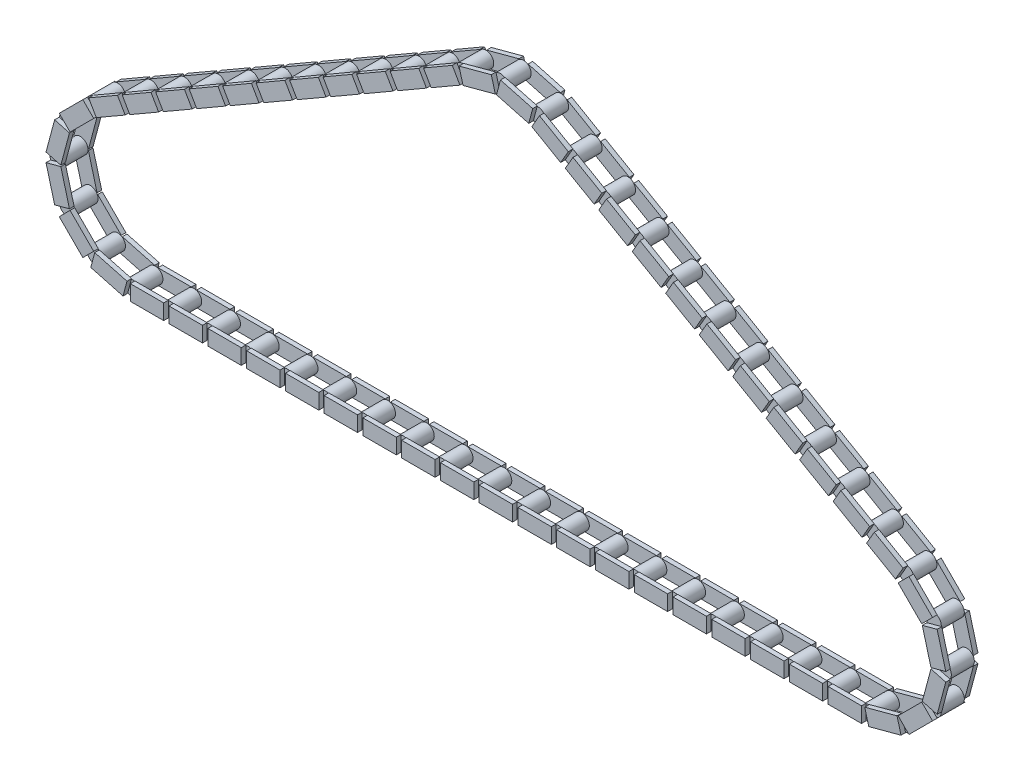
SolidWorks part; units mm, degrees
ref_plane "前视基准面" through (0, 0, 0) normal (0, 0, 1) x (1, 0, 0)
ref_plane "上视基准面" through (0, 0, 0) normal (0, 1, 0) x (1, 0, 0)
ref_plane "右视基准面" through (0, 0, 0) normal (1, 0, 0) x (0, 0, -1)
other "Configuration Table"
sketch "草图1" plane through (0, 0, 0) normal (0, 0, 1) x (1, 0, 0)
  line L0 (-97.1938, -21.2725) -> (-105.6024, -19.0195)
  line L1 (-105.6024, -19.0195) -> (-104.5671, -15.1558)
  line L2 (-104.5671, -15.1558) -> (-96.1585, -17.4088)
  line L3 (-96.1585, -17.4088) -> (-97.1938, -21.2725)
  line L4 (-107.6701, -17.8257) -> (-113.8257, -11.6701)
  line L5 (-113.8257, -11.6701) -> (-110.9972, -8.8417)
  line L6 (-110.9972, -8.8417) -> (-104.8417, -14.9972)
  line L7 (-104.8417, -14.9972) -> (-107.6701, -17.8257)
  line L8 (-115.0195, -9.6024) -> (-117.2725, -1.1938)
  line L9 (-117.2725, -1.1938) -> (-113.4088, -0.1585)
  line L10 (-113.4088, -0.1585) -> (-111.1558, -8.5671)
  line L11 (-111.1558, -8.5671) -> (-115.0195, -9.6024)
  line L12 (-117.2725, 1.1938) -> (-115.0195, 9.6024)
  line L13 (-115.0195, 9.6024) -> (-111.1558, 8.5671)
  line L14 (-111.1558, 8.5671) -> (-113.4088, 0.1585)
  line L15 (-113.4088, 0.1585) -> (-117.2725, 1.1938)
  line L16 (-113.8257, 11.6701) -> (-107.6701, 17.8257)
  line L17 (-107.6701, 17.8257) -> (-104.8417, 14.9972)
  line L18 (-104.8417, 14.9972) -> (-110.9972, 8.8417)
  line L19 (-110.9972, 8.8417) -> (-113.8257, 11.6701)
  line L20 (-106.1547, 18.9885) -> (-98.6399, 23.3272)
  line L21 (-98.6399, 23.3272) -> (-96.6399, 19.8631)
  line L22 (-96.6399, 19.8631) -> (-104.1547, 15.5244)
  line L23 (-104.1547, 15.5244) -> (-106.1547, 18.9885)
  line L24 (-97.4274, 24.0272) -> (-89.9126, 28.3659)
  line L25 (-89.9126, 28.3659) -> (-87.9126, 24.9018)
  line L26 (-87.9126, 24.9018) -> (-95.4274, 20.5631)
  line L27 (-95.4274, 20.5631) -> (-97.4274, 24.0272)
  line L28 (-88.7002, 29.0659) -> (-81.1853, 33.4046)
  line L29 (-81.1853, 33.4046) -> (-79.1853, 29.9405)
  line L30 (-79.1853, 29.9405) -> (-86.7002, 25.6018)
  line L31 (-86.7002, 25.6018) -> (-88.7002, 29.0659)
  line L32 (-79.9729, 34.1046) -> (-72.4581, 38.4433)
  line L33 (-72.4581, 38.4433) -> (-70.4581, 34.9791)
  line L34 (-70.4581, 34.9791) -> (-77.9729, 30.6405)
  line L35 (-77.9729, 30.6405) -> (-79.9729, 34.1046)
  line L36 (-71.2456, 39.1433) -> (-63.7308, 43.4819)
  line L37 (-63.7308, 43.4819) -> (-61.7308, 40.0178)
  line L38 (-61.7308, 40.0178) -> (-69.2456, 35.6791)
  line L39 (-69.2456, 35.6791) -> (-71.2456, 39.1433)
  line L40 (-62.5184, 44.1819) -> (-55.0035, 48.5206)
  line L41 (-55.0035, 48.5206) -> (-53.0035, 45.0565)
  line L42 (-53.0035, 45.0565) -> (-60.5184, 40.7178)
  line L43 (-60.5184, 40.7178) -> (-62.5184, 44.1819)
  line L44 (-53.7911, 49.2206) -> (-46.2762, 53.5593)
  line L45 (-46.2762, 53.5593) -> (-44.2762, 50.0952)
  line L46 (-44.2762, 50.0952) -> (-51.7911, 45.7565)
  line L47 (-51.7911, 45.7565) -> (-53.7911, 49.2206)
  line L48 (-45.0638, 54.2593) -> (-37.549, 58.598)
  line L49 (-37.549, 58.598) -> (-35.549, 55.1339)
  line L50 (-35.549, 55.1339) -> (-43.0638, 50.7952)
  line L51 (-43.0638, 50.7952) -> (-45.0638, 54.2593)
  line L52 (-36.3365, 59.298) -> (-28.8217, 63.6367)
  line L53 (-28.8217, 63.6367) -> (-26.8217, 60.1726)
  line L54 (-26.8217, 60.1726) -> (-34.3365, 55.8339)
  line L55 (-34.3365, 55.8339) -> (-36.3365, 59.298)
  line L56 (-27.6093, 64.3367) -> (-20.0944, 68.6754)
  line L57 (-20.0944, 68.6754) -> (-18.0944, 65.2113)
  line L58 (-18.0944, 65.2113) -> (-25.6093, 60.8726)
  line L59 (-25.6093, 60.8726) -> (-27.6093, 64.3367)
  line L60 (-18.882, 69.3754) -> (-11.3671, 73.7141)
  line L61 (-11.3671, 73.7141) -> (-9.3671, 70.25)
  line L62 (-9.3671, 70.25) -> (-16.882, 65.9113)
  line L63 (-16.882, 65.9113) -> (-18.882, 69.3754)
  line L64 (-9.6024, 74.4451) -> (-1.1938, 76.6981)
  line L65 (-1.1938, 76.6981) -> (-0.1585, 72.8344)
  line L66 (-0.1585, 72.8344) -> (-8.5671, 70.5814)
  line L67 (-8.5671, 70.5814) -> (-9.6024, 74.4451)
  line L68 (1.1938, 76.6981) -> (9.6024, 74.4451)
  line L69 (9.6024, 74.4451) -> (8.5672, 70.5814)
  line L70 (8.5672, 70.5814) -> (0.1585, 72.8344)
  line L71 (0.1585, 72.8344) -> (1.1938, 76.6981)
  line L72 (11.3672, 73.7141) -> (18.882, 69.3754)
  line L73 (18.882, 69.3754) -> (16.882, 65.9113)
  line L74 (16.882, 65.9113) -> (9.3672, 70.25)
  line L75 (9.3672, 70.25) -> (11.3672, 73.7141)
  line L76 (20.0944, 68.6754) -> (27.6093, 64.3367)
  line L77 (27.6093, 64.3367) -> (25.6093, 60.8726)
  line L78 (25.6093, 60.8726) -> (18.0944, 65.2113)
  line L79 (18.0944, 65.2113) -> (20.0944, 68.6754)
  line L80 (28.8217, 63.6367) -> (36.3365, 59.298)
  line L81 (36.3365, 59.298) -> (34.3365, 55.8339)
  line L82 (34.3365, 55.8339) -> (26.8217, 60.1726)
  line L83 (26.8217, 60.1726) -> (28.8217, 63.6367)
  line L84 (37.549, 58.598) -> (45.0638, 54.2593)
  line L85 (45.0638, 54.2593) -> (43.0638, 50.7952)
  line L86 (43.0638, 50.7952) -> (35.549, 55.1339)
  line L87 (35.549, 55.1339) -> (37.549, 58.598)
  line L88 (46.2762, 53.5593) -> (53.7911, 49.2206)
  line L89 (53.7911, 49.2206) -> (51.7911, 45.7565)
  line L90 (51.7911, 45.7565) -> (44.2762, 50.0952)
  line L91 (44.2762, 50.0952) -> (46.2762, 53.5593)
  line L92 (55.0035, 48.5206) -> (62.5184, 44.1819)
  line L93 (62.5184, 44.1819) -> (60.5184, 40.7178)
  line L94 (60.5184, 40.7178) -> (53.0035, 45.0565)
  line L95 (53.0035, 45.0565) -> (55.0035, 48.5206)
  line L96 (63.7308, 43.4819) -> (71.2456, 39.1432)
  line L97 (71.2456, 39.1432) -> (69.2456, 35.6791)
  line L98 (69.2456, 35.6791) -> (61.7308, 40.0178)
  line L99 (61.7308, 40.0178) -> (63.7308, 43.4819)
  line L100 (72.4581, 38.4433) -> (79.9729, 34.1046)
  line L101 (79.9729, 34.1046) -> (77.9729, 30.6405)
  line L102 (77.9729, 30.6405) -> (70.4581, 34.9791)
  line L103 (70.4581, 34.9791) -> (72.4581, 38.4433)
  line L104 (81.1853, 33.4046) -> (88.7002, 29.0659)
  line L105 (88.7002, 29.0659) -> (86.7002, 25.6018)
  line L106 (86.7002, 25.6018) -> (79.1853, 29.9405)
  line L107 (79.1853, 29.9405) -> (81.1853, 33.4046)
  line L108 (89.9126, 28.3659) -> (97.4274, 24.0272)
  line L109 (97.4274, 24.0272) -> (95.4274, 20.5631)
  line L110 (95.4274, 20.5631) -> (87.9126, 24.9018)
  line L111 (87.9126, 24.9018) -> (89.9126, 28.3659)
  line L112 (98.6399, 23.3272) -> (106.1547, 18.9885)
  line L113 (106.1547, 18.9885) -> (104.1547, 15.5244)
  line L114 (104.1547, 15.5244) -> (96.6399, 19.8631)
  line L115 (96.6399, 19.8631) -> (98.6399, 23.3272)
  line L116 (107.6701, 17.8257) -> (113.8257, 11.6701)
  line L117 (113.8257, 11.6701) -> (110.9972, 8.8417)
  line L118 (110.9972, 8.8417) -> (104.8417, 14.9972)
  line L119 (104.8417, 14.9972) -> (107.6701, 17.8257)
  line L120 (115.0195, 9.6024) -> (117.2725, 1.1938)
  line L121 (117.2725, 1.1938) -> (113.4088, 0.1585)
  line L122 (113.4088, 0.1585) -> (111.1558, 8.5672)
  line L123 (111.1558, 8.5672) -> (115.0195, 9.6024)
  line L124 (117.2725, -1.1938) -> (115.0195, -9.6024)
  line L125 (115.0195, -9.6024) -> (111.1558, -8.5671)
  line L126 (111.1558, -8.5671) -> (113.4088, -0.1585)
  line L127 (113.4088, -0.1585) -> (117.2725, -1.1938)
  line L128 (113.8257, -11.6701) -> (107.6701, -17.8257)
  line L129 (107.6701, -17.8257) -> (104.8417, -14.9972)
  line L130 (104.8417, -14.9972) -> (110.9972, -8.8417)
  line L131 (110.9972, -8.8417) -> (113.8257, -11.6701)
  line L132 (105.6024, -19.0195) -> (97.1938, -21.2725)
  line L133 (97.1938, -21.2725) -> (96.1585, -17.4088)
  line L134 (96.1585, -17.4088) -> (104.5672, -15.1558)
  line L135 (104.5672, -15.1558) -> (105.6024, -19.0195)
  line L136 (95.3, -21.5219) -> (86.5947, -21.5219)
  line L137 (86.5947, -21.5219) -> (86.5947, -17.5219)
  line L138 (86.5947, -17.5219) -> (95.3, -17.5219)
  line L139 (95.3, -17.5219) -> (95.3, -21.5219)
  line L140 (85.1947, -21.5219) -> (76.4895, -21.5219)
  line L141 (76.4895, -21.5219) -> (76.4895, -17.5219)
  line L142 (76.4895, -17.5219) -> (85.1947, -17.5219)
  line L143 (85.1947, -17.5219) -> (85.1947, -21.5219)
  line L144 (75.0895, -21.5219) -> (66.3842, -21.5219)
  line L145 (66.3842, -21.5219) -> (66.3842, -17.5219)
  line L146 (66.3842, -17.5219) -> (75.0895, -17.5219)
  line L147 (75.0895, -17.5219) -> (75.0895, -21.5219)
  line L148 (64.9842, -21.5219) -> (56.279, -21.5219)
  line L149 (56.279, -21.5219) -> (56.279, -17.5219)
  line L150 (56.279, -17.5219) -> (64.9842, -17.5219)
  line L151 (64.9842, -17.5219) -> (64.9842, -21.5219)
  line L152 (54.879, -21.5219) -> (46.1737, -21.5219)
  line L153 (46.1737, -21.5219) -> (46.1737, -17.5219)
  line L154 (46.1737, -17.5219) -> (54.879, -17.5219)
  line L155 (54.879, -17.5219) -> (54.879, -21.5219)
  line L156 (44.7737, -21.5219) -> (36.0684, -21.5219)
  line L157 (36.0684, -21.5219) -> (36.0684, -17.5219)
  line L158 (36.0684, -17.5219) -> (44.7737, -17.5219)
  line L159 (44.7737, -17.5219) -> (44.7737, -21.5219)
  line L160 (34.6684, -21.5219) -> (25.9632, -21.5219)
  line L161 (25.9632, -21.5219) -> (25.9632, -17.5219)
  line L162 (25.9632, -17.5219) -> (34.6684, -17.5219)
  line L163 (34.6684, -17.5219) -> (34.6684, -21.5219)
  line L164 (24.5632, -21.5219) -> (15.8579, -21.5219)
  line L165 (15.8579, -21.5219) -> (15.8579, -17.5219)
  line L166 (15.8579, -17.5219) -> (24.5632, -17.5219)
  line L167 (24.5632, -17.5219) -> (24.5632, -21.5219)
  line L168 (14.4579, -21.5219) -> (5.7526, -21.5219)
  line L169 (5.7526, -21.5219) -> (5.7526, -17.5219)
  line L170 (5.7526, -17.5219) -> (14.4579, -17.5219)
  line L171 (14.4579, -17.5219) -> (14.4579, -21.5219)
  line L172 (4.3526, -21.5219) -> (-4.3526, -21.5219)
  line L173 (-4.3526, -21.5219) -> (-4.3526, -17.5219)
  line L174 (-4.3526, -17.5219) -> (4.3526, -17.5219)
  line L175 (4.3526, -17.5219) -> (4.3526, -21.5219)
  line L176 (-5.7526, -21.5219) -> (-14.4579, -21.5219)
  line L177 (-14.4579, -21.5219) -> (-14.4579, -17.5219)
  line L178 (-14.4579, -17.5219) -> (-5.7526, -17.5219)
  line L179 (-5.7526, -17.5219) -> (-5.7526, -21.5219)
  line L180 (-15.8579, -21.5219) -> (-24.5632, -21.5219)
  line L181 (-24.5632, -21.5219) -> (-24.5632, -17.5219)
  line L182 (-24.5632, -17.5219) -> (-15.8579, -17.5219)
  line L183 (-15.8579, -17.5219) -> (-15.8579, -21.5219)
  line L184 (-25.9632, -21.5219) -> (-34.6684, -21.5219)
  line L185 (-34.6684, -21.5219) -> (-34.6684, -17.5219)
  line L186 (-34.6684, -17.5219) -> (-25.9632, -17.5219)
  line L187 (-25.9632, -17.5219) -> (-25.9632, -21.5219)
  line L188 (-36.0684, -21.5219) -> (-44.7737, -21.5219)
  line L189 (-44.7737, -21.5219) -> (-44.7737, -17.5219)
  line L190 (-44.7737, -17.5219) -> (-36.0684, -17.5219)
  line L191 (-36.0684, -17.5219) -> (-36.0684, -21.5219)
  line L192 (-46.1737, -21.5219) -> (-54.8789, -21.5219)
  line L193 (-54.8789, -21.5219) -> (-54.8789, -17.5219)
  line L194 (-54.8789, -17.5219) -> (-46.1737, -17.5219)
  line L195 (-46.1737, -17.5219) -> (-46.1737, -21.5219)
  line L196 (-56.2789, -21.5219) -> (-64.9842, -21.5219)
  line L197 (-64.9842, -21.5219) -> (-64.9842, -17.5219)
  line L198 (-64.9842, -17.5219) -> (-56.2789, -17.5219)
  line L199 (-56.2789, -17.5219) -> (-56.2789, -21.5219)
  line L200 (-66.3842, -21.5219) -> (-75.0895, -21.5219)
  line L201 (-75.0895, -21.5219) -> (-75.0895, -17.5219)
  line L202 (-75.0895, -17.5219) -> (-66.3842, -17.5219)
  line L203 (-66.3842, -17.5219) -> (-66.3842, -21.5219)
  line L204 (-76.4895, -21.5219) -> (-85.1947, -21.5219)
  line L205 (-85.1947, -21.5219) -> (-85.1947, -17.5219)
  line L206 (-85.1947, -17.5219) -> (-76.4895, -17.5219)
  line L207 (-76.4895, -17.5219) -> (-76.4895, -21.5219)
  line L208 (-86.5947, -21.5219) -> (-95.3, -21.5219)
  line L209 (-95.3, -21.5219) -> (-95.3, -17.5219)
  line L210 (-95.3, -17.5219) -> (-86.5947, -17.5219)
  line L211 (-86.5947, -17.5219) -> (-86.5947, -21.5219)
extrude "Bottom_link_plates" add sketch "草图1" along normal blind 1.2
ref_plane "Chain_plane_Rollers" through (0, 0, 1.2) normal (0, 0, 1) x (1, 0, 0)
sketch "草图3" plane through (0, 0, 1.2) normal (0, 0, 1) x (1, 0, 0)
  circle A0 centre (-96, -19.5219) radius 2
  circle A1 centre (-105.7609, -16.9064) radius 2
  circle A2 centre (-112.9064, -9.7609) radius 2
  circle A3 centre (-115.5219, 0) radius 2
  circle A4 centre (-112.9064, 9.7609) radius 2
  circle A5 centre (-105.7609, 16.9064) radius 2
  circle A6 centre (-97.0337, 21.9451) radius 2
  circle A7 centre (-88.3064, 26.9838) radius 2
  circle A8 centre (-79.5791, 32.0225) radius 2
  circle A9 centre (-70.8518, 37.0612) radius 2
  circle A10 centre (-62.1246, 42.0999) radius 2
  circle A11 centre (-53.3973, 47.1386) radius 2
  circle A12 centre (-44.67, 52.1773) radius 2
  circle A13 centre (-35.9428, 57.216) radius 2
  circle A14 centre (-27.2155, 62.2547) radius 2
  circle A15 centre (-18.4882, 67.2933) radius 2
  circle A16 centre (-9.7609, 72.332) radius 2
  circle A17 centre (0, 74.9475) radius 2
  circle A18 centre (9.7609, 72.332) radius 2
  circle A19 centre (18.4882, 67.2933) radius 2
  circle A20 centre (27.2155, 62.2547) radius 2
  circle A21 centre (35.9428, 57.216) radius 2
  circle A22 centre (44.67, 52.1773) radius 2
  circle A23 centre (53.3973, 47.1386) radius 2
  circle A24 centre (62.1246, 42.0999) radius 2
  circle A25 centre (70.8518, 37.0612) radius 2
  circle A26 centre (79.5791, 32.0225) radius 2
  circle A27 centre (88.3064, 26.9838) radius 2
  circle A28 centre (97.0337, 21.9451) radius 2
  circle A29 centre (105.7609, 16.9064) radius 2
  circle A30 centre (112.9064, 9.7609) radius 2
  circle A31 centre (115.5219, 0) radius 2
  circle A32 centre (112.9064, -9.7609) radius 2
  circle A33 centre (105.7609, -16.9064) radius 2
  circle A34 centre (96, -19.5219) radius 2
  circle A35 centre (85.8947, -19.5219) radius 2
  circle A36 centre (75.7895, -19.5219) radius 2
  circle A37 centre (65.6842, -19.5219) radius 2
  circle A38 centre (55.579, -19.5219) radius 2
  circle A39 centre (45.4737, -19.5219) radius 2
  circle A40 centre (35.3684, -19.5219) radius 2
  circle A41 centre (25.2632, -19.5219) radius 2
  circle A42 centre (15.1579, -19.5219) radius 2
  circle A43 centre (5.0526, -19.5219) radius 2
  circle A44 centre (-5.0526, -19.5219) radius 2
  circle A45 centre (-15.1579, -19.5219) radius 2
  circle A46 centre (-25.2632, -19.5219) radius 2
  circle A47 centre (-35.3684, -19.5219) radius 2
  circle A48 centre (-45.4737, -19.5219) radius 2
  circle A49 centre (-55.5789, -19.5219) radius 2
  circle A50 centre (-65.6842, -19.5219) radius 2
  circle A51 centre (-75.7895, -19.5219) radius 2
  circle A52 centre (-85.8947, -19.5219) radius 2
extrude "Rollers" add sketch "草图3" along normal blind 6
ref_plane "Chain_plane_Top_link_plates" through (0, 0, 7.2) normal (0, 0, 1) x (1, 0, 0)
sketch "草图5" plane through (0, 0, 7.2) normal (0, 0, 1) x (1, 0, 0)
  line L0 (-97.1938, -21.2725) -> (-105.6024, -19.0195)
  line L1 (-105.6024, -19.0195) -> (-104.5671, -15.1558)
  line L2 (-104.5671, -15.1558) -> (-96.1585, -17.4088)
  line L3 (-96.1585, -17.4088) -> (-97.1938, -21.2725)
  line L4 (-107.6701, -17.8257) -> (-113.8257, -11.6701)
  line L5 (-113.8257, -11.6701) -> (-110.9972, -8.8417)
  line L6 (-110.9972, -8.8417) -> (-104.8417, -14.9972)
  line L7 (-104.8417, -14.9972) -> (-107.6701, -17.8257)
  line L8 (-115.0195, -9.6024) -> (-117.2725, -1.1938)
  line L9 (-117.2725, -1.1938) -> (-113.4088, -0.1585)
  line L10 (-113.4088, -0.1585) -> (-111.1558, -8.5671)
  line L11 (-111.1558, -8.5671) -> (-115.0195, -9.6024)
  line L12 (-117.2725, 1.1938) -> (-115.0195, 9.6024)
  line L13 (-115.0195, 9.6024) -> (-111.1558, 8.5671)
  line L14 (-111.1558, 8.5671) -> (-113.4088, 0.1585)
  line L15 (-113.4088, 0.1585) -> (-117.2725, 1.1938)
  line L16 (-113.8257, 11.6701) -> (-107.6701, 17.8257)
  line L17 (-107.6701, 17.8257) -> (-104.8417, 14.9972)
  line L18 (-104.8417, 14.9972) -> (-110.9972, 8.8417)
  line L19 (-110.9972, 8.8417) -> (-113.8257, 11.6701)
  line L20 (-106.1547, 18.9885) -> (-98.6399, 23.3272)
  line L21 (-98.6399, 23.3272) -> (-96.6399, 19.8631)
  line L22 (-96.6399, 19.8631) -> (-104.1547, 15.5244)
  line L23 (-104.1547, 15.5244) -> (-106.1547, 18.9885)
  line L24 (-97.4274, 24.0272) -> (-89.9126, 28.3659)
  line L25 (-89.9126, 28.3659) -> (-87.9126, 24.9018)
  line L26 (-87.9126, 24.9018) -> (-95.4274, 20.5631)
  line L27 (-95.4274, 20.5631) -> (-97.4274, 24.0272)
  line L28 (-88.7002, 29.0659) -> (-81.1853, 33.4046)
  line L29 (-81.1853, 33.4046) -> (-79.1853, 29.9405)
  line L30 (-79.1853, 29.9405) -> (-86.7002, 25.6018)
  line L31 (-86.7002, 25.6018) -> (-88.7002, 29.0659)
  line L32 (-79.9729, 34.1046) -> (-72.4581, 38.4433)
  line L33 (-72.4581, 38.4433) -> (-70.4581, 34.9791)
  line L34 (-70.4581, 34.9791) -> (-77.9729, 30.6405)
  line L35 (-77.9729, 30.6405) -> (-79.9729, 34.1046)
  line L36 (-71.2456, 39.1433) -> (-63.7308, 43.4819)
  line L37 (-63.7308, 43.4819) -> (-61.7308, 40.0178)
  line L38 (-61.7308, 40.0178) -> (-69.2456, 35.6791)
  line L39 (-69.2456, 35.6791) -> (-71.2456, 39.1433)
  line L40 (-62.5184, 44.1819) -> (-55.0035, 48.5206)
  line L41 (-55.0035, 48.5206) -> (-53.0035, 45.0565)
  line L42 (-53.0035, 45.0565) -> (-60.5184, 40.7178)
  line L43 (-60.5184, 40.7178) -> (-62.5184, 44.1819)
  line L44 (-53.7911, 49.2206) -> (-46.2762, 53.5593)
  line L45 (-46.2762, 53.5593) -> (-44.2762, 50.0952)
  line L46 (-44.2762, 50.0952) -> (-51.7911, 45.7565)
  line L47 (-51.7911, 45.7565) -> (-53.7911, 49.2206)
  line L48 (-45.0638, 54.2593) -> (-37.549, 58.598)
  line L49 (-37.549, 58.598) -> (-35.549, 55.1339)
  line L50 (-35.549, 55.1339) -> (-43.0638, 50.7952)
  line L51 (-43.0638, 50.7952) -> (-45.0638, 54.2593)
  line L52 (-36.3365, 59.298) -> (-28.8217, 63.6367)
  line L53 (-28.8217, 63.6367) -> (-26.8217, 60.1726)
  line L54 (-26.8217, 60.1726) -> (-34.3365, 55.8339)
  line L55 (-34.3365, 55.8339) -> (-36.3365, 59.298)
  line L56 (-27.6093, 64.3367) -> (-20.0944, 68.6754)
  line L57 (-20.0944, 68.6754) -> (-18.0944, 65.2113)
  line L58 (-18.0944, 65.2113) -> (-25.6093, 60.8726)
  line L59 (-25.6093, 60.8726) -> (-27.6093, 64.3367)
  line L60 (-18.882, 69.3754) -> (-11.3671, 73.7141)
  line L61 (-11.3671, 73.7141) -> (-9.3671, 70.25)
  line L62 (-9.3671, 70.25) -> (-16.882, 65.9113)
  line L63 (-16.882, 65.9113) -> (-18.882, 69.3754)
  line L64 (-9.6024, 74.4451) -> (-1.1938, 76.6981)
  line L65 (-1.1938, 76.6981) -> (-0.1585, 72.8344)
  line L66 (-0.1585, 72.8344) -> (-8.5671, 70.5814)
  line L67 (-8.5671, 70.5814) -> (-9.6024, 74.4451)
  line L68 (1.1938, 76.6981) -> (9.6024, 74.4451)
  line L69 (9.6024, 74.4451) -> (8.5672, 70.5814)
  line L70 (8.5672, 70.5814) -> (0.1585, 72.8344)
  line L71 (0.1585, 72.8344) -> (1.1938, 76.6981)
  line L72 (11.3672, 73.7141) -> (18.882, 69.3754)
  line L73 (18.882, 69.3754) -> (16.882, 65.9113)
  line L74 (16.882, 65.9113) -> (9.3672, 70.25)
  line L75 (9.3672, 70.25) -> (11.3672, 73.7141)
  line L76 (20.0944, 68.6754) -> (27.6093, 64.3367)
  line L77 (27.6093, 64.3367) -> (25.6093, 60.8726)
  line L78 (25.6093, 60.8726) -> (18.0944, 65.2113)
  line L79 (18.0944, 65.2113) -> (20.0944, 68.6754)
  line L80 (28.8217, 63.6367) -> (36.3365, 59.298)
  line L81 (36.3365, 59.298) -> (34.3365, 55.8339)
  line L82 (34.3365, 55.8339) -> (26.8217, 60.1726)
  line L83 (26.8217, 60.1726) -> (28.8217, 63.6367)
  line L84 (37.549, 58.598) -> (45.0638, 54.2593)
  line L85 (45.0638, 54.2593) -> (43.0638, 50.7952)
  line L86 (43.0638, 50.7952) -> (35.549, 55.1339)
  line L87 (35.549, 55.1339) -> (37.549, 58.598)
  line L88 (46.2762, 53.5593) -> (53.7911, 49.2206)
  line L89 (53.7911, 49.2206) -> (51.7911, 45.7565)
  line L90 (51.7911, 45.7565) -> (44.2762, 50.0952)
  line L91 (44.2762, 50.0952) -> (46.2762, 53.5593)
  line L92 (55.0035, 48.5206) -> (62.5184, 44.1819)
  line L93 (62.5184, 44.1819) -> (60.5184, 40.7178)
  line L94 (60.5184, 40.7178) -> (53.0035, 45.0565)
  line L95 (53.0035, 45.0565) -> (55.0035, 48.5206)
  line L96 (63.7308, 43.4819) -> (71.2456, 39.1432)
  line L97 (71.2456, 39.1432) -> (69.2456, 35.6791)
  line L98 (69.2456, 35.6791) -> (61.7308, 40.0178)
  line L99 (61.7308, 40.0178) -> (63.7308, 43.4819)
  line L100 (72.4581, 38.4433) -> (79.9729, 34.1046)
  line L101 (79.9729, 34.1046) -> (77.9729, 30.6405)
  line L102 (77.9729, 30.6405) -> (70.4581, 34.9791)
  line L103 (70.4581, 34.9791) -> (72.4581, 38.4433)
  line L104 (81.1853, 33.4046) -> (88.7002, 29.0659)
  line L105 (88.7002, 29.0659) -> (86.7002, 25.6018)
  line L106 (86.7002, 25.6018) -> (79.1853, 29.9405)
  line L107 (79.1853, 29.9405) -> (81.1853, 33.4046)
  line L108 (89.9126, 28.3659) -> (97.4274, 24.0272)
  line L109 (97.4274, 24.0272) -> (95.4274, 20.5631)
  line L110 (95.4274, 20.5631) -> (87.9126, 24.9018)
  line L111 (87.9126, 24.9018) -> (89.9126, 28.3659)
  line L112 (98.6399, 23.3272) -> (106.1547, 18.9885)
  line L113 (106.1547, 18.9885) -> (104.1547, 15.5244)
  line L114 (104.1547, 15.5244) -> (96.6399, 19.8631)
  line L115 (96.6399, 19.8631) -> (98.6399, 23.3272)
  line L116 (107.6701, 17.8257) -> (113.8257, 11.6701)
  line L117 (113.8257, 11.6701) -> (110.9972, 8.8417)
  line L118 (110.9972, 8.8417) -> (104.8417, 14.9972)
  line L119 (104.8417, 14.9972) -> (107.6701, 17.8257)
  line L120 (115.0195, 9.6024) -> (117.2725, 1.1938)
  line L121 (117.2725, 1.1938) -> (113.4088, 0.1585)
  line L122 (113.4088, 0.1585) -> (111.1558, 8.5672)
  line L123 (111.1558, 8.5672) -> (115.0195, 9.6024)
  line L124 (117.2725, -1.1938) -> (115.0195, -9.6024)
  line L125 (115.0195, -9.6024) -> (111.1558, -8.5671)
  line L126 (111.1558, -8.5671) -> (113.4088, -0.1585)
  line L127 (113.4088, -0.1585) -> (117.2725, -1.1938)
  line L128 (113.8257, -11.6701) -> (107.6701, -17.8257)
  line L129 (107.6701, -17.8257) -> (104.8417, -14.9972)
  line L130 (104.8417, -14.9972) -> (110.9972, -8.8417)
  line L131 (110.9972, -8.8417) -> (113.8257, -11.6701)
  line L132 (105.6024, -19.0195) -> (97.1938, -21.2725)
  line L133 (97.1938, -21.2725) -> (96.1585, -17.4088)
  line L134 (96.1585, -17.4088) -> (104.5672, -15.1558)
  line L135 (104.5672, -15.1558) -> (105.6024, -19.0195)
  line L136 (95.3, -21.5219) -> (86.5947, -21.5219)
  line L137 (86.5947, -21.5219) -> (86.5947, -17.5219)
  line L138 (86.5947, -17.5219) -> (95.3, -17.5219)
  line L139 (95.3, -17.5219) -> (95.3, -21.5219)
  line L140 (85.1947, -21.5219) -> (76.4895, -21.5219)
  line L141 (76.4895, -21.5219) -> (76.4895, -17.5219)
  line L142 (76.4895, -17.5219) -> (85.1947, -17.5219)
  line L143 (85.1947, -17.5219) -> (85.1947, -21.5219)
  line L144 (75.0895, -21.5219) -> (66.3842, -21.5219)
  line L145 (66.3842, -21.5219) -> (66.3842, -17.5219)
  line L146 (66.3842, -17.5219) -> (75.0895, -17.5219)
  line L147 (75.0895, -17.5219) -> (75.0895, -21.5219)
  line L148 (64.9842, -21.5219) -> (56.279, -21.5219)
  line L149 (56.279, -21.5219) -> (56.279, -17.5219)
  line L150 (56.279, -17.5219) -> (64.9842, -17.5219)
  line L151 (64.9842, -17.5219) -> (64.9842, -21.5219)
  line L152 (54.879, -21.5219) -> (46.1737, -21.5219)
  line L153 (46.1737, -21.5219) -> (46.1737, -17.5219)
  line L154 (46.1737, -17.5219) -> (54.879, -17.5219)
  line L155 (54.879, -17.5219) -> (54.879, -21.5219)
  line L156 (44.7737, -21.5219) -> (36.0684, -21.5219)
  line L157 (36.0684, -21.5219) -> (36.0684, -17.5219)
  line L158 (36.0684, -17.5219) -> (44.7737, -17.5219)
  line L159 (44.7737, -17.5219) -> (44.7737, -21.5219)
  line L160 (34.6684, -21.5219) -> (25.9632, -21.5219)
  line L161 (25.9632, -21.5219) -> (25.9632, -17.5219)
  line L162 (25.9632, -17.5219) -> (34.6684, -17.5219)
  line L163 (34.6684, -17.5219) -> (34.6684, -21.5219)
  line L164 (24.5632, -21.5219) -> (15.8579, -21.5219)
  line L165 (15.8579, -21.5219) -> (15.8579, -17.5219)
  line L166 (15.8579, -17.5219) -> (24.5632, -17.5219)
  line L167 (24.5632, -17.5219) -> (24.5632, -21.5219)
  line L168 (14.4579, -21.5219) -> (5.7526, -21.5219)
  line L169 (5.7526, -21.5219) -> (5.7526, -17.5219)
  line L170 (5.7526, -17.5219) -> (14.4579, -17.5219)
  line L171 (14.4579, -17.5219) -> (14.4579, -21.5219)
  line L172 (4.3526, -21.5219) -> (-4.3526, -21.5219)
  line L173 (-4.3526, -21.5219) -> (-4.3526, -17.5219)
  line L174 (-4.3526, -17.5219) -> (4.3526, -17.5219)
  line L175 (4.3526, -17.5219) -> (4.3526, -21.5219)
  line L176 (-5.7526, -21.5219) -> (-14.4579, -21.5219)
  line L177 (-14.4579, -21.5219) -> (-14.4579, -17.5219)
  line L178 (-14.4579, -17.5219) -> (-5.7526, -17.5219)
  line L179 (-5.7526, -17.5219) -> (-5.7526, -21.5219)
  line L180 (-15.8579, -21.5219) -> (-24.5632, -21.5219)
  line L181 (-24.5632, -21.5219) -> (-24.5632, -17.5219)
  line L182 (-24.5632, -17.5219) -> (-15.8579, -17.5219)
  line L183 (-15.8579, -17.5219) -> (-15.8579, -21.5219)
  line L184 (-25.9632, -21.5219) -> (-34.6684, -21.5219)
  line L185 (-34.6684, -21.5219) -> (-34.6684, -17.5219)
  line L186 (-34.6684, -17.5219) -> (-25.9632, -17.5219)
  line L187 (-25.9632, -17.5219) -> (-25.9632, -21.5219)
  line L188 (-36.0684, -21.5219) -> (-44.7737, -21.5219)
  line L189 (-44.7737, -21.5219) -> (-44.7737, -17.5219)
  line L190 (-44.7737, -17.5219) -> (-36.0684, -17.5219)
  line L191 (-36.0684, -17.5219) -> (-36.0684, -21.5219)
  line L192 (-46.1737, -21.5219) -> (-54.8789, -21.5219)
  line L193 (-54.8789, -21.5219) -> (-54.8789, -17.5219)
  line L194 (-54.8789, -17.5219) -> (-46.1737, -17.5219)
  line L195 (-46.1737, -17.5219) -> (-46.1737, -21.5219)
  line L196 (-56.2789, -21.5219) -> (-64.9842, -21.5219)
  line L197 (-64.9842, -21.5219) -> (-64.9842, -17.5219)
  line L198 (-64.9842, -17.5219) -> (-56.2789, -17.5219)
  line L199 (-56.2789, -17.5219) -> (-56.2789, -21.5219)
  line L200 (-66.3842, -21.5219) -> (-75.0895, -21.5219)
  line L201 (-75.0895, -21.5219) -> (-75.0895, -17.5219)
  line L202 (-75.0895, -17.5219) -> (-66.3842, -17.5219)
  line L203 (-66.3842, -17.5219) -> (-66.3842, -21.5219)
  line L204 (-76.4895, -21.5219) -> (-85.1947, -21.5219)
  line L205 (-85.1947, -21.5219) -> (-85.1947, -17.5219)
  line L206 (-85.1947, -17.5219) -> (-76.4895, -17.5219)
  line L207 (-76.4895, -17.5219) -> (-76.4895, -21.5219)
  line L208 (-86.5947, -21.5219) -> (-95.3, -21.5219)
  line L209 (-95.3, -21.5219) -> (-95.3, -17.5219)
  line L210 (-95.3, -17.5219) -> (-86.5947, -17.5219)
  line L211 (-86.5947, -17.5219) -> (-86.5947, -21.5219)
extrude "Top_link_plates" add sketch "草图5" along normal blind 1.2
